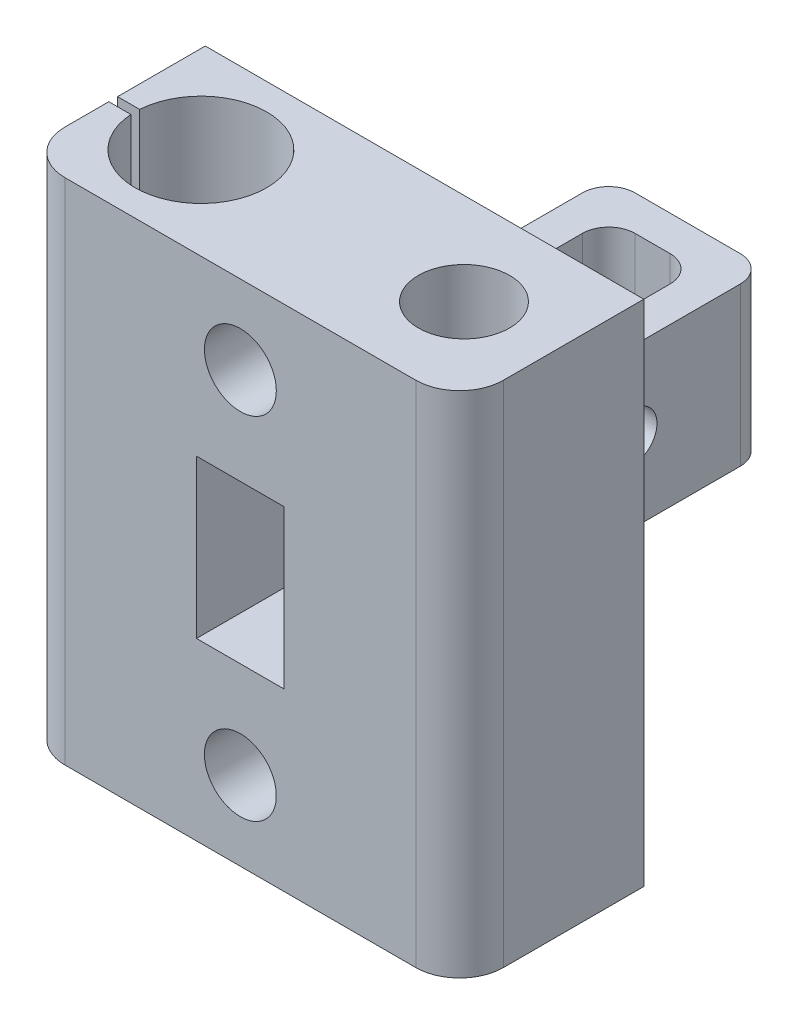
SolidWorks part; units mm, degrees
ref_plane "Front Plane" through (0, 0, 0) normal (0, 0, 1) x (1, 0, 0)
ref_plane "Top Plane" through (0, 0, 0) normal (0, 1, 0) x (1, 0, 0)
ref_plane "Right Plane" through (0, 0, 0) normal (1, 0, 0) x (0, 0, -1)
sketch "Sketch1" plane through (0, 0, 0) normal (0, 1, 0) x (1, 0, 0)
  line L1 (-25, 10.5) -> (25, 10.5)
  line L2 (-25, 10.5) -> (-25, -10.5)
  line L3 (-25, -10.5) -> (25, -10.5)
  line L4 (25, 10.5) -> (25, -10.5)
  line L5 (-25, 10.5) -> (25, -10.5) construction
  line L6 (-25, -10.5) -> (25, 10.5) construction
  point P0 (0, 0)
  dimension "D1" = 21
  dimension "D2" = 50
extrude "Boss-Extrude1" add sketch "Sketch1" along normal blind 58
sketch "Sketch3" plane through (0, 58, 0) normal (0, 1, 0) x (1, 0, 0)
  line L0 (-15, 0) -> (15, 0) construction
  circle A0 centre (-15, 0) radius 7.5
  dimension "D1" = 15
  dimension "D2" = 30
extrude "Cut-Extrude1" cut sketch "Sketch3" against normal blind 24 contours A0
sketch "Sketch4" plane through (0, 58, 0) normal (0, 1, 0) x (1, 0, 0)
  line L0 (-15, 0) -> (15, 0) construction
  circle A0 centre (15, 0) radius 5.2
  dimension "D1" = 10.4
extrude "Cut-Extrude2" cut sketch "Sketch4" against normal up to next
sketch "Sketch5" plane through (0, 0, 0) normal (0, -1, 0) x (1, 0, 0)
  circle A1 centre (-15, 0) radius 7.5
  circle A2 centre (-15, 0) radius 7.5
  dimension "D1" = 0
extrude "Cut-Extrude3" cut sketch "Sketch5" against normal blind 24
sketch "Sketch6" plane through (0, 0, 0) normal (0, -1, 0) x (1, 0, 0)
  circle A0 centre (-15, 0) radius 4.5
extrude "Cut-Extrude4" cut sketch "Sketch6" against normal up to next
sketch "Sketch7" plane through (0, 0, 10.5) normal (0, 0, 1) x (1, 0, 0)
  line L0 (0, 58) -> (0, 0) construction
  line L1 (-25, 58) -> (25, 58) construction
  line L2 (-25, 0) -> (25, 0) construction
  line L3 (-25, 29) -> (25, 29) construction
  line L4 (-25, 58) -> (-25, 0) construction
  line L5 (25, 58) -> (25, 0) construction
  circle A1 centre (0, 49) radius 4.1
  circle A2 centre (0, 9) radius 4.1
  point P24 (0, 9)
  dimension "D1" = 8.2
  dimension "D2" = 9
sketch "Sketch8" plane through (0, 0, 10.5) normal (0, 0, 1) x (1, 0, 0)
  line L0 (-25, 29) -> (25, 29) construction
  line L1 (-25, 58) -> (-25, 0) construction
  line L2 (25, 58) -> (25, 0) construction
  line L3 (0, 58) -> (0, 0) construction
  line L4 (-25, 58) -> (25, 58) construction
  line L6 (-5, 20) -> (5, 20)
  line L7 (-5, 20) -> (-5, 38)
  line L8 (-5, 38) -> (5, 38)
  line L9 (5, 20) -> (5, 38)
  line L10 (-5, 20) -> (5, 38) construction
  line L11 (-5, 38) -> (5, 20) construction
  point P11 (0, 29)
  dimension "D1" = 18
  dimension "D2" = 10
extrude "Cut-Extrude5" cut sketch "Sketch8" against normal up to next
sketch "Sketch10" plane through (0, 0, -10.5) normal (0, 0, -1) x (-1, 0, 0)
  line L0 (-25, 29) -> (25, 29) construction
  line L1 (-25, 58) -> (-25, 0) construction
  line L2 (25, 58) -> (25, 0) construction
  line L3 (0, 58) -> (0, 0) construction
  line L4 (-25, 58) -> (25, 58) construction
extrude "Cut-Extrude6" cut sketch "Sketch7" against normal blind 15
sketch "Sketch11" plane through (0, 0, -10.5) normal (0, 0, -1) x (-1, 0, 0)
  line L0 (-25, 29) -> (25, 29) construction
  line L1 (9, 38) -> (5, 38)
  line L2 (9, 38) -> (9, 20)
  line L3 (9, 20) -> (5, 20)
  line L4 (5, 38) -> (5, 20)
  line L5 (9, 38) -> (5, 20) construction
  line L6 (9, 20) -> (5, 38) construction
  line L7 (0, 58) -> (0, 0) construction
  line L8 (0, 58) -> (0, 0)
  line L9 (-9, 20) -> (-5, 20)
  line L10 (-5, 38) -> (-5, 20)
  line L11 (-9, 38) -> (-5, 38)
  line L12 (-9, 38) -> (-9, 20)
  point P0 (7, 29)
  line M7 (-5, 20) -> (-5, 38)
  line M9 (5, 38) -> (5, 20)
  dimension "D1" = 5
  dimension "D2" = 4
  dimension "D3" = 18
extrude "Boss-Extrude2" add sketch "Sketch11" along normal blind 26 contours L1 L4 L3 L2 M9 | L11 L12 L9 L10 M7 region at (-7, 29, -10.5) region at (7, 29, -10.5)
sketch "Sketch12" plane through (0, 0, -36.5) normal (0, 0, -1) x (-1, 0, 0)
  line L1 (9, 20) -> (-9, 20)
  line L2 (9, 20) -> (9, 38)
  line L3 (9, 38) -> (-9, 38)
  line L4 (-9, 20) -> (-9, 38)
extrude "Boss-Extrude3" add sketch "Sketch12" along normal blind 4
sketch "Sketch13" plane through (9, 0, 0) normal (1, 0, 0) x (0, 0, -1)
  line L3 (10.5, 29) -> (40.5, 29) construction
  line L4 (10.5, 38) -> (10.5, 20) construction
  line L5 (40.5, 38) -> (40.5, 20) construction
  line L6 (16.25, 29) -> (25.25, 29) construction
  line L7 (16.25, 31.75) -> (25.25, 31.75)
  line L8 (16.25, 26.25) -> (25.25, 26.25)
  arc A0 (16.25, 31.75) -> (16.25, 26.25) centre (16.25, 29) ccw
  arc A1 (25.25, 26.25) -> (25.25, 31.75) centre (25.25, 29) ccw
  point P1 (13.5, 29)
  point P14 (20.75, 29)
  dimension "D1" = 5.5
  dimension "D2" = 3
  dimension "D3" = 9
extrude "Cut-Extrude7" cut sketch "Sketch13" against normal through all
fillet "Fillet1" radius 5 2 edges at (-25, 29, 10.5) (25, 29, 10.5)
fillet "Fillet2" radius 5 4 edges at (-7, 20, -10.5) (7, 20, -10.5) (-7, 38, -10.5) (7, 38, -10.5)
fillet "Fillet3" radius 3 4 edges at (-5, 29, -36.5) (5, 29, -36.5) (-9, 29, -40.5) (9, 29, -40.5)
sketch "Sketch14" plane through (0, 0, 0) normal (0, -1, 0) x (1, 0, 0)
  line L0 (20.5508, 5.5508) -> (9.4492, -5.5508) construction
  line L1 (25, -10.5) -> (-25, -10.5) construction
  circle A0 centre (20.5508, 5.5508) radius 1.95
  circle A1 centre (15, 0) radius 5.2 construction
  circle A2 centre (9.4492, -5.5508) radius 1.95
  circle A3 centre (15, 0) radius 5.2 construction
  dimension "D1" = 7.85
  dimension "D2" = 3.9
  dimension "D3" = 3.9
  dimension "D4" = 7.85
  dimension "D5" = 45
extrude "Cut-Extrude8" cut sketch "Sketch14" against normal blind 10
sketch "Sketch15" plane through (0, 58, 0) normal (0, 1, 0) x (1, 0, 0)
  line L0 (-25, 10.5) -> (-25, -5.5) construction
  line L1 (-25, -0.5) -> (-19.4721, -0.5)
  line L2 (-25, -0.5) -> (-25, 0.5)
  line L3 (-25, 0.5) -> (-19.4721, 0.5)
  line L4 (-19.4721, -0.5) -> (-19.4721, 0.5)
  circle A2 centre (-15, 0) radius 4.5 construction
  dimension "D1" = 1
extrude "Cut-Extrude9" cut sketch "Sketch15" against normal through all
